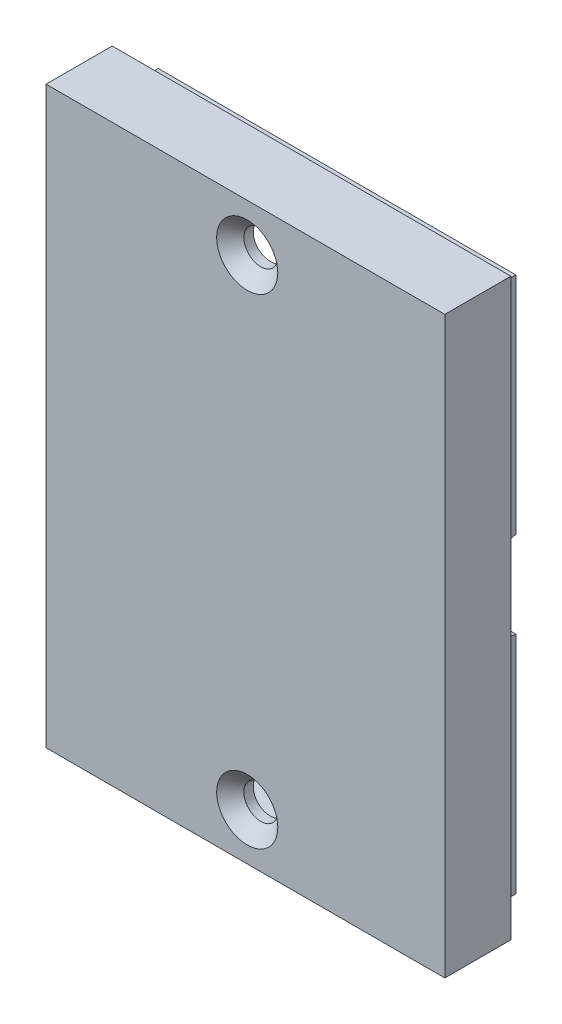
SolidWorks part; units mm, degrees
material "PET"
ref_plane "Front Plane" through (0, 0, 0) normal (0, 0, 1) x (1, 0, 0)
ref_plane "Top Plane" through (0, 0, 0) normal (0, 1, 0) x (1, 0, 0)
ref_plane "Right Plane" through (0, 0, 0) normal (1, 0, 0) x (0, 0, -1)
sketch "Sketch1" plane through (0, 0, 0) normal (0, 0, 1) x (1, 0, 0)
  line L0 (31.75, 23.8125) -> (33.3375, 23.8125) construction
  line L1 (0, 0) -> (31.75, 0)
  line L2 (0, 0) -> (0, 47.625)
  line L3 (0, 47.625) -> (31.75, 47.625)
  line L4 (31.75, 0) -> (31.75, 47.625)
  line L5 (33.3375, 49.2125) -> (-12.7, 49.2125)
  line L6 (33.3375, 49.2125) -> (33.3375, -1.5875)
  line L7 (33.3375, -1.5875) -> (-12.7, -1.5875)
  line L8 (-12.7, 49.2125) -> (-12.7, -1.5875)
  dimension "D1" = 31.75
  dimension "D2" = 47.625
  dimension "D3" = 50.8
  dimension "D4" = 12.7
  dimension "D5" = 1.5875
sketch "Sketch2" plane through (0, 0, 0) normal (0, 0, 1) x (1, 0, 0)
  line L1 (0.127, 47.498) -> (31.75, 47.498)
  line L2 (0.127, 47.498) -> (0.127, 0.127)
  line L3 (0.127, 0.127) -> (31.75, 0.127)
  line L4 (31.75, 47.498) -> (31.75, 0.127)
  line L5 (31.75, 0) -> (31.75, 47.625) construction
  line L6 (0.635, 46.99) -> (31.115, 46.99)
  line L7 (0.635, 46.99) -> (0.635, 0.635)
  line L8 (0.635, 0.635) -> (31.115, 0.635)
  line L9 (31.115, 46.99) -> (31.115, 0.635)
  line L10 (0, 47.625) -> (31.75, 47.625) construction
  line L11 (0, 0) -> (0, 47.625) construction
  line L12 (0, 0) -> (31.75, 0) construction
  point P4 (31.75, 0)
  point P5 (0, 47.625)
  point P15 (0.6362, 46.99)
  point P18 (0.1639, 47.4219)
  point P21 (31.75, 0.4036)
  dimension "D1" = 0.635
  dimension "D2" = 0.635
  dimension "D3" = 0.127
  dimension "D4" = 0.127
  dimension "D5" = 0.635
  dimension "D6" = 0.127
  dimension "D7" = 0.635
extrude "Boss-Extrude1" add sketch "Sketch2" along normal blind 2.032
sketch "Sketch3" plane through (0, 0, 2.032) normal (0, 0, 1) x (1, 0, 0)
  line L0 (33.3375, 49.2125) -> (-12.7, 49.2125) construction
  line L1 (0.635, 46.99) -> (31.115, 46.99)
  line L2 (0.635, 46.99) -> (0.635, 0.635)
  line L3 (0.635, 0.635) -> (31.115, 0.635)
  line L4 (31.115, 46.99) -> (31.115, 0.635)
  line L5 (33.3375, -1.5875) -> (-1.905, -1.5875)
  line L6 (33.3375, -1.5875) -> (33.3375, 49.2125)
  line L7 (33.3375, 49.2125) -> (-1.905, 49.2125)
  line L8 (-1.905, -1.5875) -> (-1.905, 49.2125)
  line L9 (0, 0) -> (0, 47.625) construction
  dimension "D1" = 1.905
extrude "Boss-Extrude2" add sketch "Sketch3" along normal blind 3.81
sketch "Sketch4" plane through (0, 0, 5.842) normal (0, 0, 1) x (1, 0, 0)
  line L1 (-1.905, 49.2125) -> (33.3375, 49.2125)
  line L2 (-1.905, 49.2125) -> (-1.905, -1.5875)
  line L3 (-1.905, -1.5875) -> (33.3375, -1.5875)
  line L4 (33.3375, 49.2125) -> (33.3375, -1.5875)
extrude "Boss-Extrude3" add sketch "Sketch4" along normal blind 2.032
sketch "Sketch5" plane through (31.75, 0, 0) normal (1, 0, 0) x (0, 0, -1)
  line L0 (0, 26.3525) -> (0, 21.2725) construction
  line L2 (1.27, 26.3525) -> (1.27, 21.2725)
  line L3 (-1.27, 26.3525) -> (-1.27, 21.2725)
  line L4 (0, 0.127) -> (0, 47.498) construction
  arc A0 (1.27, 26.3525) -> (-1.27, 26.3525) centre (0, 26.3525) ccw
  arc A1 (-1.27, 21.2725) -> (1.27, 21.2725) centre (0, 21.2725) ccw
  point P2 (-0.5176, 23.7147)
  point P3 (0, 0)
  point P4 (0, 23.8125)
  point P9 (0, 0)
  dimension "D1" = 5.08
  dimension "D2" = 2.54
extrude "Cut-Extrude1" cut sketch "Sketch5" against normal up to next
sketch "Sketch6" plane through (0.127, 0, 0) normal (-1, 0, 0) x (0, 0, 1)
  line L0 (0, 47.498) -> (0, 0.127) construction
  line L1 (0, 46.99) -> (1.778, 46.99)
  line L2 (0, 46.99) -> (0, 44.45)
  line L3 (0, 44.45) -> (1.778, 44.45)
  line L4 (1.778, 46.99) -> (1.778, 44.45)
  line L6 (2.032, 47.498) -> (2.032, 0.127) construction
  line L7 (0, 0.635) -> (1.778, 0.635)
  line L8 (0, 0.635) -> (0, 3.175)
  line L9 (0, 3.175) -> (1.778, 3.175)
  line L10 (1.778, 0.635) -> (1.778, 3.175)
  line L11 (5.842, 0.635) -> (0, 0.635) construction
  line L13 (0, 25.0825) -> (1.778, 25.0825)
  line L14 (0, 25.0825) -> (0, 22.5425)
  line L15 (0, 22.5425) -> (1.778, 22.5425)
  line L16 (1.778, 25.0825) -> (1.778, 22.5425)
  line L17 (1.778, 23.8125) -> (7.874, 23.8125) construction
  line L21 (2.032, 49.2125) -> (2.032, -1.5875) construction
  line L22 (7.874, 49.2125) -> (7.874, -1.5875) construction
  point P24 (6.5654, 23.1365)
  point P25 (0, 0)
  dimension "D1" = 0.254
  dimension "D2" = 0.254
  dimension "D3" = 2.54
  dimension "D4" = 2.54
  dimension "D5" = 0.254
  dimension "D6" = 2.54
extrude "Cut-Extrude2" cut sketch "Sketch6" against normal up to next
fillet "Fillet1" radius 1.27 6 edges at (0.381, 3.175, 1.778) (0.381, 0.635, 1.778) (0.381, 22.5425, 1.778) (0.381, 25.0825, 1.778) (0.381, 46.99, 1.778) (0.381, 44.45, 1.778)
sketch "Sketch7" plane through (0, 0, 7.874) normal (0, 0, 1) x (1, 0, 0)
  point P0 (15.875, 45.0169)
  point P1 (15.875, 2.5646)
hole_wizard "CSK for M3 Flat Head Machine Screw1" positions "Sketch8" profile "Sketch9" countersink size "M3" standard "ANSI Metric" end condition through all
sketch "Sketch8" plane through (0, 0, 7.874) normal (0, 0, 1) x (1, 0, 0)
  point P0 (15.875, 2.5646)
  point P3 (15.875, 45.0169)
sketch "Sketch9" plane through (15.875, 2.5646, 7.874) normal (1, 0, 0) x (0, -1, 0)
  line L0 (0, 0) -> (0, 7.874)
  line L1 (0, 7.874) -> (1.5, 7.874)
  line L2 (1.5, 7.874) -> (1.5, 1.2)
  line L3 (1.5, 1.2) -> (2.7, 0)
  line L5 (2.7, 0) -> (0, 0)
  line L6 (-1.5, 1.2) -> (-2.7, 0) construction
  line L11 (0, -6.35) -> (0, 107.95) construction
  dimension "Thru Hole Dia." = 3
  dimension "Thru Hole Depth" = 7.874
  dimension "Near C'Sink Dia." = 5.4
  dimension "Near C'Sink Angle" = 90
